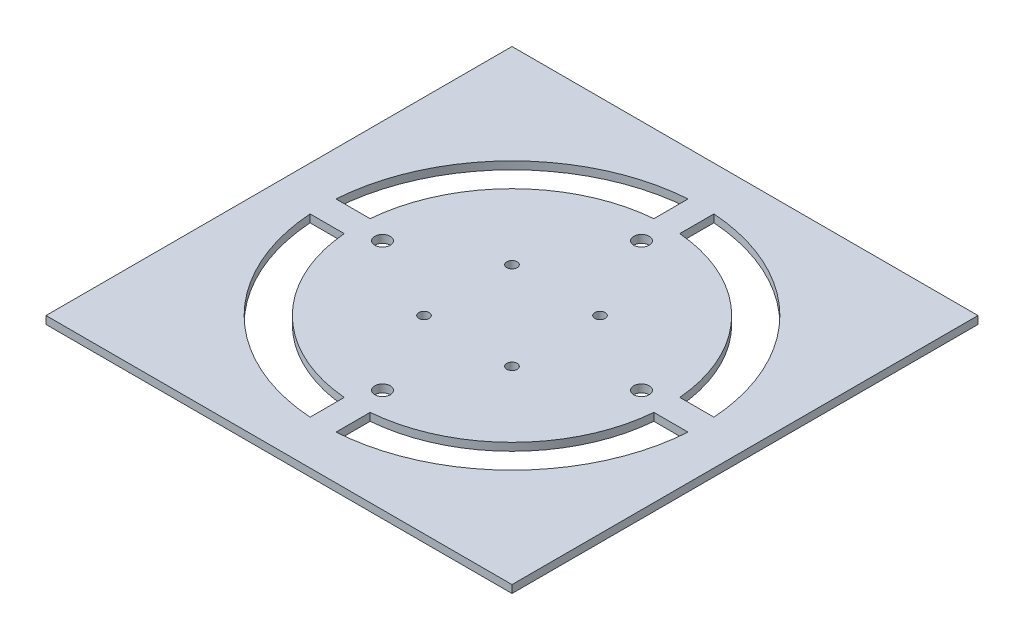
SolidWorks part; units mm, degrees
ref_plane "前视基准面" through (0, 0, 0) normal (0, 0, 1) x (1, 0, 0)
ref_plane "上视基准面" through (0, 0, 0) normal (0, 1, 0) x (1, 0, 0)
ref_plane "右视基准面" through (0, 0, 0) normal (1, 0, 0) x (0, 0, -1)
sketch "草图1" plane through (0, 0, 0) normal (0, 1, 0) x (1, 0, 0)
  line L0 (0, -28.3374) -> (0, 58.5252) construction
  line L1 (-49.5021, 0) -> (67.6509, 0) construction
  line L2 (-45, 45) -> (45, 45)
  line L3 (45, 45) -> (45, -45)
  line L4 (-45, 45) -> (-45, -45)
  line L5 (-45, -45) -> (45, -45)
  line L6 (29.8957, 2.5) -> (36.4957, 2.5)
  line L7 (29.8957, -2.5) -> (36.4957, -2.5)
  line L8 (2.5, 36.4957) -> (2.5, 29.8957)
  line L9 (-2.5, 36.4957) -> (-2.5, 29.8957)
  line L10 (-2.5, -36.4957) -> (-2.5, -29.8957)
  line L11 (2.5, -36.4957) -> (2.5, -29.8957)
  line L12 (-29.8957, -2.5) -> (-36.4957, -2.5)
  line L13 (-29.8957, 2.5) -> (-36.4957, 2.5)
  arc A0 (29.8957, 2.5) -> (2.5, 29.8957) centre (0, 0) ccw
  arc A1 (36.4957, 2.5) -> (2.5, 36.4957) centre (0, 0) ccw
  arc A2 (-29.8957, -2.5) -> (-2.5, -29.8957) centre (0, 0) ccw
  arc A3 (-36.4957, -2.5) -> (-2.5, -36.4957) centre (0, 0) ccw
  arc A4 (-2.5, 29.8957) -> (-29.8957, 2.5) centre (0, 0) ccw
  arc A5 (-2.5, 36.4957) -> (-36.4957, 2.5) centre (0, 0) ccw
  arc A6 (2.5, -36.4957) -> (36.4957, -2.5) centre (0, 0) ccw
  arc A7 (2.5, -29.8957) -> (29.8957, -2.5) centre (0, 0) ccw
  circle A8 centre (0, 0) radius 25 construction
  circle A9 centre (0, 25) radius 1.5
  circle A10 centre (25, 0) radius 1.5
  circle A11 centre (0, -25) radius 1.5
  circle A12 centre (-25, 0) radius 1.5
  circle A13 centre (8.5, 8.5) radius 1
  circle A14 centre (-8.5, 8.5) radius 1
  circle A15 centre (8.5, -8.5) radius 1
  circle A16 centre (-8.5, -8.5) radius 1
  point P13 (0, 45)
  point P14 (45, 0)
  point P15 (-45, 0)
  dimension "D1" = 5
  dimension "D4" = 60
  dimension "D7" = 50
  dimension "D8" = 3
  dimension "D9" = 3
  dimension "D10" = 3
  dimension "D11" = 3
  dimension "D12" = 2
  dimension "D13" = 17
  dimension "D14" = 17
  dimension "D2" = 5
  dimension "D3" = 6.6
  dimension "D5" = 90
  dimension "D6" = 90
extrude "凸台-拉伸1" add sketch "草图1" along normal blind 1.5
